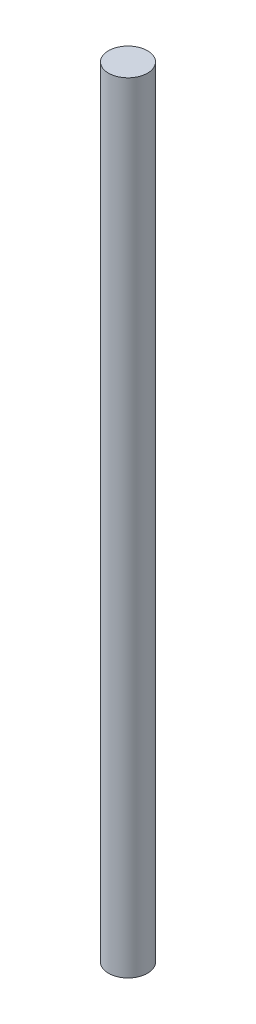
SolidWorks part; units mm, degrees
ref_plane "Front Plane" through (0, 0, 0) normal (0, 0, 1) x (1, 0, 0)
ref_plane "Top Plane" through (0, 0, 0) normal (0, 1, 0) x (1, 0, 0)
ref_plane "Right Plane" through (0, 0, 0) normal (1, 0, 0) x (0, 0, -1)
sketch "Sketch1" plane through (0, 0, 0) normal (0, 1, 0) x (1, 0, 0)
  circle A0 centre (0, 0) radius 3
  dimension "D1" = 6
extrude "Boss-Extrude1" add sketch "Sketch1" along normal blind 120
